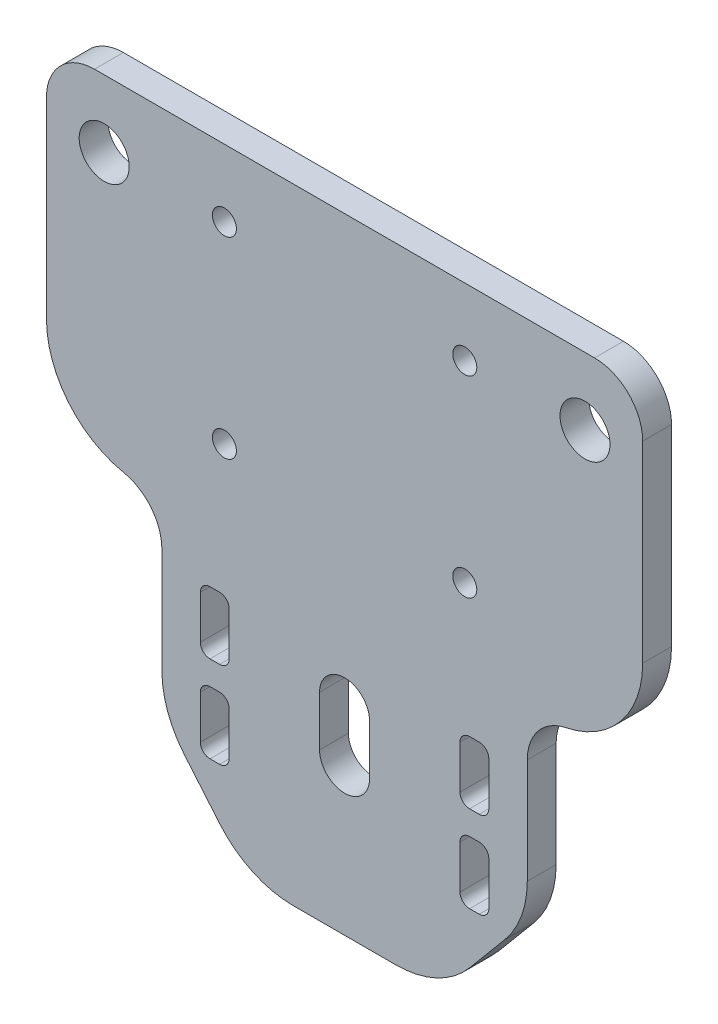
SolidWorks part; units mm, degrees
note: '?' marks a value the reader was unsure of.
material "AISI 4340 Steel, annealed"
ref_plane "Front Plane" through (0, 0, 0) normal (0, 0, 1) x (1, 0, 0)
ref_plane "Top Plane" through (0, 0, 0) normal (0, 1, 0) x (1, 0, 0)
ref_plane "Right Plane" through (0, 0, 0) normal (1, 0, 0) x (0, 0, -1)
sketch "Sketch1" plane through (0, 0, 0) normal (0, 0, 1) x (1, 0, 0)
  line L0 (0, 3.5) -> (0, -65.4767) construction
  line L1 (-31, -0.4767) -> (31, -0.4767)
  line L2 (31, -0.4767) -> (31, -35.4767)
  line L3 (19, -54.7521) -> (10, -65.4767)
  line L4 (10, -65.4767) -> (-10, -65.4767)
  line L5 (-10, -65.4767) -> (-19, -54.7521)
  line L6 (-31, -35.4767) -> (-31, -0.4767)
  line L7 (0, -50.0767) -> (0, -44.8767) construction
  line L8 (-2.6, -50.0767) -> (-2.6, -44.8767)
  line L9 (2.6, -50.0767) -> (2.6, -44.8767)
  line L10 (25, -7.4767) -> (-25, -7.4767) construction
  line L11 (-49.3871, -27.4767) -> (47.6915, -27.4767) construction
  line L12 (-31, -35.4767) -> (-19, -35.4767)
  line L13 (-19, -35.4767) -> (-19, -54.7521)
  line L15 (19, -35.4767) -> (19, -54.7521)
  line L16 (31, -35.4767) -> (19, -35.4767)
  circle A0 centre (25, -7.4767) radius 2.6
  circle A1 centre (-25, -7.4767) radius 2.6
  circle A2 centre (0, -47.4767) radius 2.6 construction
  arc A3 (-2.6, -50.0767) -> (2.6, -50.0767) centre (0, -50.0767) ccw
  arc A4 (2.6, -44.8767) -> (-2.6, -44.8767) centre (0, -44.8767) ccw
  circle A5 centre (-12.5, -27.4767) radius 1.25
  circle A6 centre (12.5, -27.4767) radius 1.25
  circle A7 centre (12.5, -7.4767) radius 1.25
  circle A8 centre (-12.5, -7.4767) radius 1.25
  point P17 (0, -47.4767)
  dimension "D4" = 50
  dimension "D6" = 5.2
  dimension "D8" = 7
  dimension "D9" = 20
  dimension "D10" = 2.5
  dimension "D1" = 62
  dimension "D2" = 35
  dimension "D3" = 20
  dimension "D5" = 40
  dimension "D7" = 65
  dimension "D11" = 25
  dimension "D12" = 12.5
  dimension "D13" = 25
  dimension "D14" = 12.5
  dimension "D15" = 12
base flange "Base-Flange1" sketch "Sketch1" thickness 3 reverse thickness direction no parameters "D1"=5
fillet "Fillet1" radius 5 2 edges at (31, -0.4767, -1.5) (-31, -0.4767, -1.5)
fillet "Fillet2" radius 10 6 edges at (-10, -65.4767, -1.5) (10, -65.4767, -1.5) (-31, -35.4767, -1.5) (31, -35.4767, -1.5) (19, -54.7521, -1.5) (-19, -54.7521, -1.5)
ref_axis "Axis1" through (-500.3795, -57.5767, 0) along (1, 0, 0)?
sketch "Sketch3" plane through (0, 0, 0) normal (0, 0, 1) x (1, 0, 0)
  line L0 (0, -55.7419) -> (0, -24.8829) construction
  line L1 (12, -41.0767) -> (15, -41.0767)
  line L2 (12, -41.0767) -> (12, -47.5767)
  line L3 (12, -47.5767) -> (15, -47.5767)
  line L4 (15, -41.0767) -> (15, -47.5767)
  line L9 (12, -50.0767) -> (15, -50.0767)
  line L10 (12, -50.0767) -> (12, -56.5767)
  line L11 (12, -56.5767) -> (15, -56.5767)
  line L12 (15, -50.0767) -> (15, -56.5767)
extrude "Cut-Extrude1" cut sketch "Sketch3" against normal up to next normal cut yes
fillet "Fillet3" radius 1 8 edges at (12, -50.0767, -1.5) (15, -50.0767, -1.5) (15, -56.5767, -1.5) (12, -56.5767, -1.5) (12, -47.5767, -1.5) (15, -47.5767, -1.5) (15, -41.0767, -1.5) (12, -41.0767, -1.5)
ref_plane "Plane1" through (0, 0, 0) normal (1, 0, 0) x (0, 0, -1)
mirror "Mirror1" about plane through (0, 0, 0) normal (1, 0, 0) of "Cut-Extrude1", "Fillet3"
fillet "Fillet4" radius 5 2 edges at (19, -35.4767, -1.5) (-19, -35.4767, -1.5)
sketch "Bend-Lines1" [suppressed] plane through (0, 0, 0) normal (0, 1, 0) x (1, 0, 0)
sketch "Bounding-Box1" [suppressed] plane through (0, 0, 0) normal (0, 1, 0) x (1, 0, 0)
sheet metal parameters "Sheet-Metal1" thickness 3 parameters "D1"=5
flat pattern "Flat-Pattern1" [suppressed]
sketch "Bend-Lines2" plane through (0, 0, 0) normal (0, 1, 0) x (1, 0, 0)
sketch3d "Bounding-Box2" [suppressed]
  line L0 (31, -0.4767, 0) -> (31, -65.4767, 0) construction
  line L1 (-31, -0.4767, 0) -> (-31, -65.4767, 0) construction
  line L2 (31, -0.4767, 0) -> (-31, -0.4767, 0) construction
  line L3 (31, -65.4767, 0) -> (-31, -65.4767, 0) construction
sheet metal parameters "Sheet-Metal3" thickness 3 parameters "D1"=5
flat pattern "Flat-Pattern1"
sketch "Bend-Lines2" plane through (0, 0, 0) normal (0, 1, 0) x (1, 0, 0)
sketch3d "Bounding-Box2" [suppressed]
  line L0 (31, -0.4767, 0) -> (31, -65.4767, 0) construction
  line L1 (-31, -0.4767, 0) -> (-31, -65.4767, 0) construction
  line L2 (31, -0.4767, 0) -> (-31, -0.4767, 0) construction
  line L3 (31, -65.4767, 0) -> (-31, -65.4767, 0) construction
sheet metal parameters "Sheet-Metal4" thickness 3 parameters "D1"=5
flat pattern "Flat-Pattern1"
sketch "Bend-Lines2" plane through (0, 0, 0) normal (0, 1, 0) x (1, 0, 0)
sketch3d "Bounding-Box2" [suppressed]
  line L0 (31, -0.4767, 0) -> (31, -65.4767, 0) construction
  line L1 (-31, -0.4767, 0) -> (-31, -65.4767, 0) construction
  line L2 (31, -0.4767, 0) -> (-31, -0.4767, 0) construction
  line L3 (31, -65.4767, 0) -> (-31, -65.4767, 0) construction
